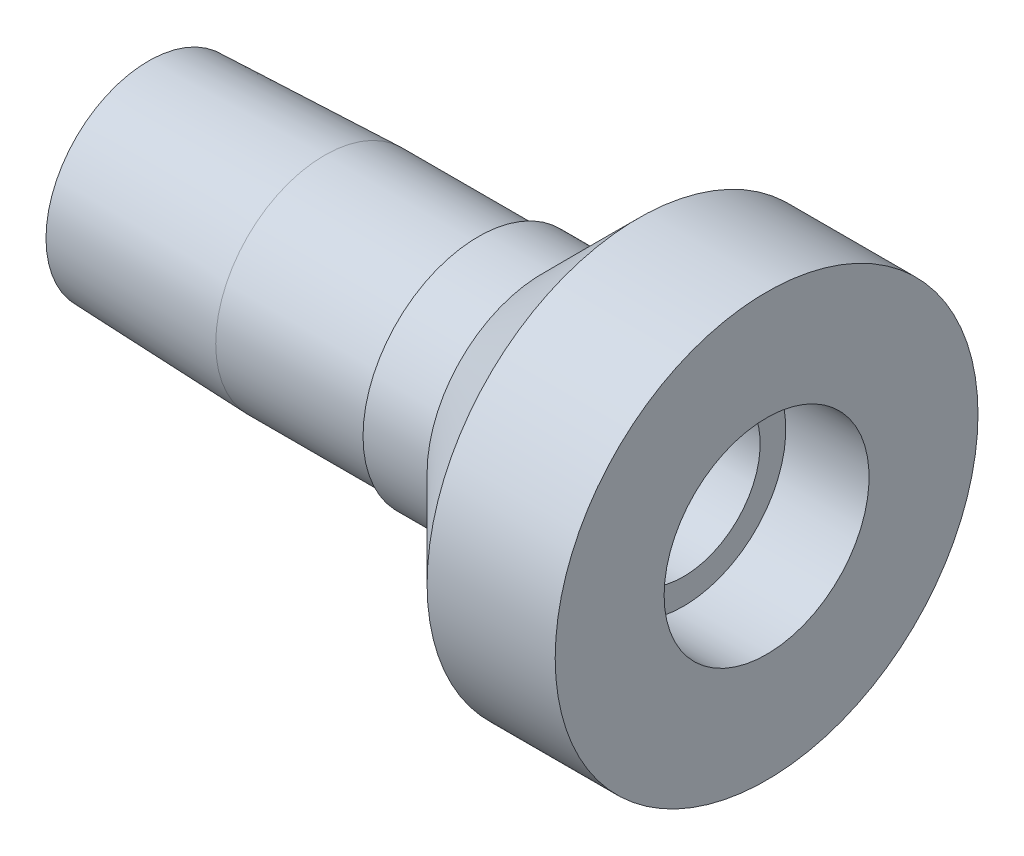
SolidWorks part; units mm, degrees
ref_plane "Front Plane" through (0, 0, 0) normal (0, 0, 1) x (1, 0, 0)
ref_plane "Top Plane" through (0, 0, 0) normal (0, 1, 0) x (1, 0, 0)
ref_plane "Right Plane" through (0, 0, 0) normal (1, 0, 0) x (0, 0, -1)
sketch "Sketch2" plane through (0, 0, 0) normal (0, 0, 1) x (1, 0, 0)
  line L0 (0, 0) -> (64.6823, 0) construction
  line L1 (0, 8) -> (0, 6)
  line L2 (0, 6) -> (41.75, 6)
  line L7 (48.25, 8) -> (48.25, 16.5024)
  line L8 (48.25, 16.5024) -> (38.25, 16.5024)
  line L11 (41.75, 6) -> (41.75, 8)
  line L12 (41.75, 8) -> (48.25, 8)
  line L15 (30.7476, 9) -> (38.25, 16.5024)
  line L16 (0, 8) -> (13.7476, 8.5)
  line L17 (13.7476, 8.5) -> (25.7476, 8.5)
  line L19 (25.7476, 8.5) -> (25.7476, 9)
  line L20 (25.7476, 9) -> (30.7476, 9)
  point P5 (8.4736, 8.5)
  point P13 (13.4076, 8.5)
  dimension "D1" = 8.5
  dimension "D2" = 6
  dimension "D3" = 8
  dimension "D4" = 6.5
  dimension "D5" = 0.5
  dimension "D6" = 45
  dimension "D7" = 10
  dimension "D8" = 41.75
  dimension "D9" = 12
  dimension "D10" = 8.5024
  dimension "D11" = 8
  dimension "D12" = 5
revolve "Revolve1" add sketch "Sketch2" angle 360 about L0
